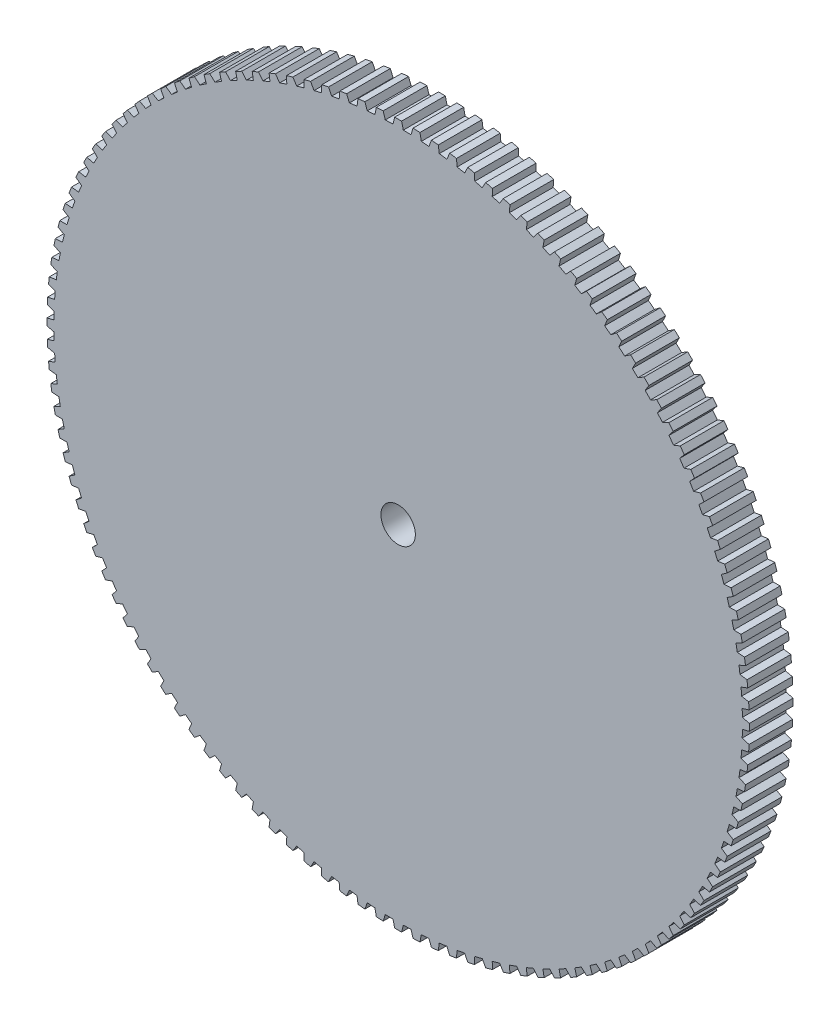
SolidWorks part; units mm, degrees
ref_plane "Front Plane" through (0, 0, 0) normal (0, 0, 1) x (1, 0, 0)
ref_plane "Top Plane" through (0, 0, 0) normal (0, 1, 0) x (1, 0, 0)
ref_plane "Right Plane" through (0, 0, 0) normal (1, 0, 0) x (0, 0, -1)
sketch "Sketch1" plane through (0, 0, 0) normal (0, 0, 1) x (1, 0, 0)
  circle A0 centre (0, 0) radius 50
  circle A1 centre (0, 0) radius 2.5
  dimension "D1" = 100
  dimension "D2" = 5
extrude "Boss-Extrude1" add sketch "Sketch1" along normal blind 6.35
sketch "Sketch2" plane through (0, 0, 6.35) normal (0, 0, 1) x (1, 0, 0)
  line L0 (0, -1000) -> (0, 49000) construction
  line L1 (0.5, -51) -> (-0.5, -51)
  line L2 (-1, -49) -> (1, -49)
  line L4 (0.5, -51) -> (1, -49)
  line L5 (-0.5, -51) -> (-1, -49)
  circle A0 centre (0, 0) radius 50 construction
  point P8 (0, -51)
  point P10 (0, -49)
  dimension "D1" = 49
  dimension "D2" = 51
  dimension "D3" = 1
  dimension "D4" = 2
extrude "Boss-Extrude2" add sketch "Sketch2" against normal blind 6.35
pattern_circular "CirPattern1" count 120 over 360 about axis through (0, 0, 6.35) along (0, 0, -1) of "Boss-Extrude2"
